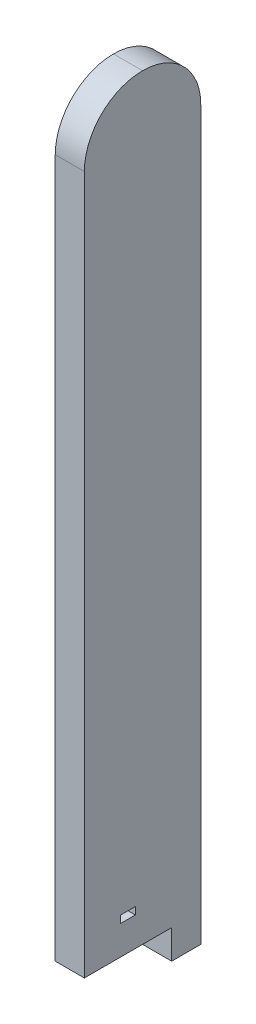
SolidWorks part; units mm, degrees
ref_plane "Front Plane" through (0, 0, 0) normal (0, 0, 1) x (1, 0, 0)
ref_plane "Top Plane" through (0, 0, 0) normal (0, 1, 0) x (1, 0, 0)
ref_plane "Right Plane" through (0, 0, 0) normal (1, 0, 0) x (0, 0, -1)
sketch "Sketch1" plane through (0, 0, 0) normal (1, 0, 0) x (0, 0, -1)
  line L0 (12.7, -69.5376) -> (12.7, -158.75)
  line L1 (-12.7, 12.7) -> (12.7, 12.7)
  line L2 (-12.7, 12.7) -> (-12.7, -152.4)
  line L3 (-12.7, -152.4) -> (6.35, -152.4)
  line L4 (12.7, 12.7) -> (12.7, -69.5376)
  line L5 (118.5159, -204.6272) -> (-242.7398, -81.778) construction
  line L7 (12.7, -158.75) -> (6.35, -158.75)
  line L8 (6.35, -158.75) -> (6.35, -152.4)
  line L9 (4.503, -155.575) -> (-49995.497, -155.575) construction
  line L11 (-12.7, 12.7) -> (0, 0) construction
  line L12 (0, 0) -> (12.7, 12.7) construction
  circle A0 centre (0, 0) radius 155.575 construction
  point P0 (0, 0)
  point P11 (6.35, -155.575)
  dimension "D1" = 25.4
  dimension "D2" = 6.35
  dimension "D3" = 6.35
extrude "Boss-Extrude1" add sketch "Sketch1" along normal mid plane 6.35
fillet "Fillet1" radius 12.7 2 edges at (0, 12.7, -12.7) (0, 12.7, 12.7)
sketch "Sketch2" plane through (3.175, 0, 0) normal (1, 0, 0) x (0, 0, -1)
  line L1 (-4.7625, -146.05) -> (-1.5875, -146.05)
  line L2 (-4.7625, -146.05) -> (-4.7625, -144.4625)
  line L3 (-4.7625, -144.4625) -> (-1.5875, -144.4625)
  line L4 (-1.5875, -146.05) -> (-1.5875, -144.4625)
  line L5 (-4.7625, -146.05) -> (-1.5875, -144.4625) construction
  line L6 (-4.7625, -144.4625) -> (-1.5875, -146.05) construction
  line L7 (-3.175, -152.4) -> (-3.175, -145.2563) construction
  line L8 (-12.7, -152.4) -> (6.35, -152.4) construction
  point P0 (-3.175, -145.2563)
  dimension "D1" = 6.35
  dimension "D2" = 1.5875
  dimension "D3" = 3.175
extrude "Cable-tie hole" cut sketch "Sketch2" against normal through all
